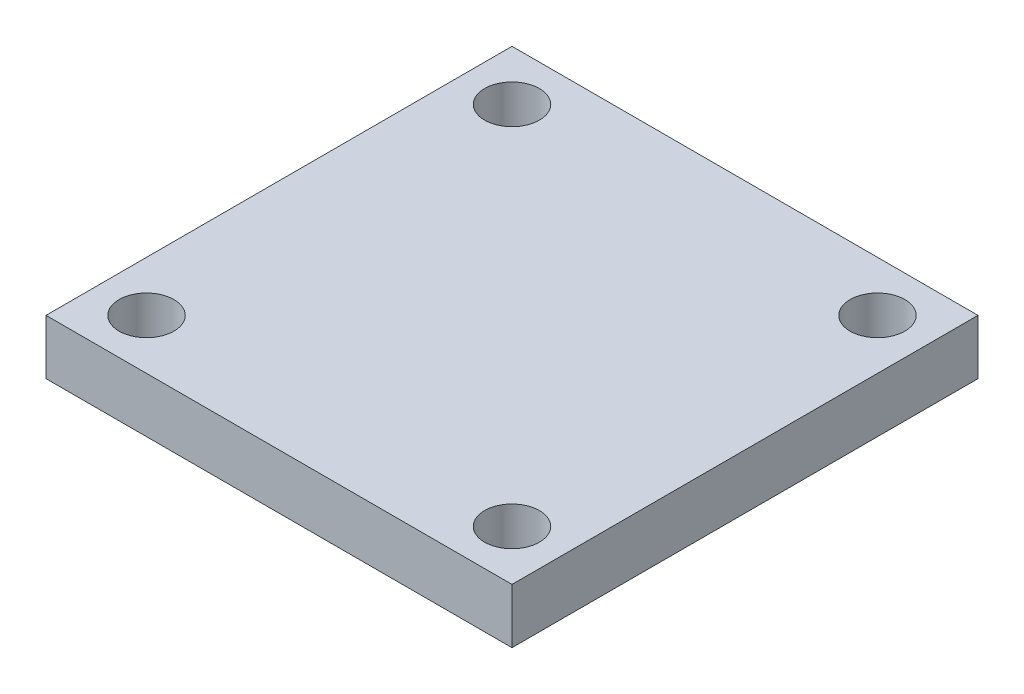
SolidWorks part; units mm, degrees
ref_plane "Front Plane" through (0, 0, 0) normal (0, 0, 1) x (1, 0, 0)
ref_plane "Top Plane" through (0, 0, 0) normal (0, 1, 0) x (1, 0, 0)
ref_plane "Right Plane" through (0, 0, 0) normal (1, 0, 0) x (0, 0, -1)
sketch "Sketch1" plane through (0, 0, 0) normal (0, 1, 0) x (1, 0, 0)
  line L0 (-30, 0) -> (-19, 0) construction
  line L1 (-19, -19) -> (19, -19)
  line L2 (-19, -19) -> (-19, 19)
  line L3 (-19, 19) -> (19, 19)
  line L4 (19, -19) -> (19, 19)
  line L5 (-19, -19) -> (19, 19) construction
  line L6 (-19, 19) -> (19, -19) construction
  line L8 (0, 18.0312) -> (18.0312, 0)
  line L9 (0, 18.0312) -> (-18.0312, 0)
  line L10 (-18.0312, 0) -> (0, -18.0312)
  line L11 (18.0312, 0) -> (0, -18.0312)
  line L12 (0, 18.0312) -> (0, -18.0312) construction
  line L13 (-18.0312, 0) -> (18.0312, 0) construction
  circle A1 centre (-24.5, 0) radius 1.5
  circle A2 centre (0, 0) radius 30
  circle A3 centre (0, 0) radius 19
  circle A4 centre (0, 18.0312) radius 1.75
  point P0 (0, 0)
  dimension "D3" = 3
  dimension "D6" = 60
  dimension "D7" = 38
  dimension "D8" = 3.5
  dimension "D2" = 38
  dimension "D4" = 25.5
  dimension "D5" = 25.5
sketch "Sketch2" plane through (0, 0, 0) normal (0, 1, 0) x (1, 0, 0)
  line L1 (-10, -10) -> (10, -10) construction
  line L2 (-10, -10) -> (-10, 10) construction
  line L3 (-10, 10) -> (10, 10) construction
  line L4 (10, -10) -> (10, 10) construction
  line L5 (-10, -10) -> (10, 10) construction
  line L6 (-10, 10) -> (10, -10) construction
  line L7 (-12.75, -12.75) -> (12.75, -12.75)
  line L8 (-12.75, -12.75) -> (-12.75, 12.75)
  line L9 (-12.75, 12.75) -> (12.75, 12.75)
  line L10 (12.75, -12.75) -> (12.75, 12.75)
  line L11 (-12.75, -12.75) -> (12.75, 12.75) construction
  line L12 (-12.75, 12.75) -> (12.75, -12.75) construction
  circle A0 centre (-10, 10) radius 1.5
  circle A1 centre (10, 10) radius 1.5
  circle A2 centre (10, -10) radius 1.5
  circle A3 centre (-10, -10) radius 1.5
  point P0 (0, 0)
  point P7 (0, 0)
  point P16 (0, 0)
  point P24 (0, 0)
  dimension "D2" = 3
  dimension "D1" = 20
  dimension "D4" = 25.5
  dimension "D3" = 4
extrude "Flight Computer" add sketch "Sketch2" along normal blind 3 contours A3 A2 A1 A0 region at (0, 0, 0)
sketch "Sketch3" plane through (0, 3, 0) normal (0, 1, 0) x (1, 0, 0)
  line L1 (-5, -5) -> (5, -5)
  line L2 (-5, -5) -> (-5, 5)
  line L3 (-5, 5) -> (5, 5)
  line L4 (5, -5) -> (5, 5)
  line L5 (-5, -5) -> (5, 5) construction
  line L6 (-5, 5) -> (5, -5) construction
  point P0 (0, 0)
  dimension "D1" = 10
